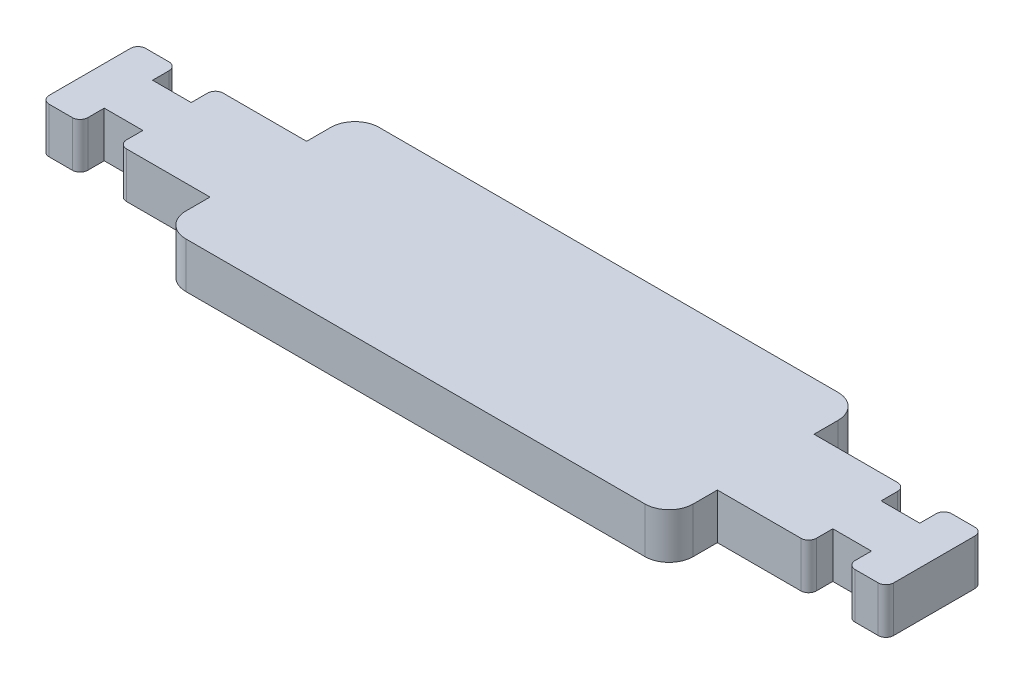
SolidWorks part; units mm, degrees
ref_plane "Front Plane" through (0, 0, 0) normal (0, 0, 1) x (1, 0, 0)
ref_plane "Top Plane" through (0, 0, 0) normal (0, 1, 0) x (1, 0, 0)
ref_plane "Right Plane" through (0, 0, 0) normal (1, 0, 0) x (0, 0, -1)
sketch "Sketch3" plane through (0, 0, 0) normal (0, 1, 0) x (1, 0, 0)
  line L0 (0, -17.5593) -> (0, 17.5593) construction
  line L1 (-19.05, 17.5593) -> (-16.05, 17.5593)
  line L2 (-19.05, 17.5593) -> (-19.05, -17.5593)
  line L3 (-19.05, -17.5593) -> (-16.05, -17.5593)
  line L4 (-16.05, 17.5593) -> (-16.05, -17.5593)
  line L5 (-19.05, 17.5593) -> (-16.05, -17.5593) construction
  line L6 (-19.05, -17.5593) -> (-16.05, 17.5593) construction
  line L7 (19.05, -17.5593) -> (16.05, 17.5593) construction
  line L8 (19.05, 17.5593) -> (16.05, -17.5593) construction
  line L9 (16.05, 17.5593) -> (16.05, -17.5593)
  line L10 (19.05, -17.5593) -> (16.05, -17.5593)
  line L11 (19.05, 17.5593) -> (19.05, -17.5593)
  line L12 (19.05, 17.5593) -> (16.05, 17.5593)
  point P0 (-17.55, 0)
  point P12 (17.55, 0)
  dimension "D1" = 3
  dimension "D2" = 38.1
sketch "Sketch1" plane through (0, 0, 0) normal (0, 1, 0) x (1, 0, 0)
  line L1 (15.0876, -6.35) -> (-15.0876, -6.35)
  line L2 (16.6751, -4.7625) -> (16.6751, 4.7625)
  line L3 (15.0876, 6.35) -> (-15.0876, 6.35)
  line L4 (-16.6751, -4.7625) -> (-16.6751, 4.7625)
  line L5 (16.6751, -6.35) -> (-16.6751, 6.35) construction
  line L6 (16.6751, 6.35) -> (-16.6751, -6.35) construction
  arc A0 (16.6751, 4.7625) -> (15.0876, 6.35) centre (15.0876, 4.7625) ccw
  arc A1 (16.6751, -4.7625) -> (15.0876, -6.35) centre (15.0876, -4.7625) cw
  arc A2 (-15.0876, -6.35) -> (-16.6751, -4.7625) centre (-15.0876, -4.7625) cw
  arc A3 (-15.0876, 6.35) -> (-16.6751, 4.7625) centre (-15.0876, 4.7625) ccw
  point P0 (0, 0)
  dimension "D3" = 1.5875
  dimension "D1" = 33.3502
  dimension "D2" = 12.7
extrude "Boss-Extrude1" add sketch "Sketch1" along normal mid plane 3
sketch "Sketch2" plane through (0, 1.5, 0) normal (0, 1, 0) x (1, 0, 0)
  line L0 (-16.6751, 4.7625) -> (-16.6751, -4.7625) construction
  line L1 (-22.6751, -3.175) -> (-16.6751, -3.175)
  line L2 (-22.6751, 1.5875) -> (-22.6751, 3.175)
  line L3 (-22.6751, 3.175) -> (-16.6751, 3.175)
  line L4 (-16.6751, -3.175) -> (-16.6751, 3.175)
  line L5 (-22.6751, -3.175) -> (-16.6751, 3.175) construction
  line L6 (-22.6751, 3.175) -> (-16.6751, -3.175) construction
  line L7 (-22.6751, -3.175) -> (-25.2151, -3.175) construction
  line L13 (-25.2151, -3.175) -> (-27.7551, -3.175)
  line L14 (-27.7551, -3.175) -> (-27.7551, 3.175)
  line L15 (-27.7551, 3.175) -> (-25.2151, 3.175)
  line L16 (-25.2151, 3.175) -> (-25.2151, 1.5875)
  line L17 (-25.2151, 1.5875) -> (-22.6751, 1.5875)
  line L18 (-22.6751, -1.5875) -> (-22.6751, 1.5875) construction
  line L19 (-22.6751, -3.175) -> (-22.6751, -1.5875)
  line L20 (-22.6751, -1.5875) -> (-25.2151, -1.5875)
  line L21 (-25.2151, -1.5875) -> (-25.2151, -3.175)
  point P0 (-19.6751, 0)
  point P5 (-16.5382, 0)
  dimension "D3" = 1.5875
  dimension "D1" = 6.35
  dimension "D2" = 6
  dimension "D4" = 2.54
  dimension "D5" = 2.54
extrude "Boss-Extrude2" add sketch "Sketch2" against normal up to surface (3 mm away) up to face at (0, -1.5, 0)
fillet "Fillet1" radius 0.508 6 edges at (-27.7551, 0, 3.175) (-27.7551, 0, -3.175) (-25.2151, 0, -3.175) (-22.6751, 0, -3.175) (-22.6751, 0, 3.175) (-25.2151, 0, 3.175)
mirror "Mirror1" about plane through (0, 0, 0) normal (1, 0, 0) of bodies 102
equation "\"D1@Sketch3\"=3mm"
equation "\"D1@Sketch1\"=1.25in+.063in"
equation "\"D2@Sketch2\"=6mm"
